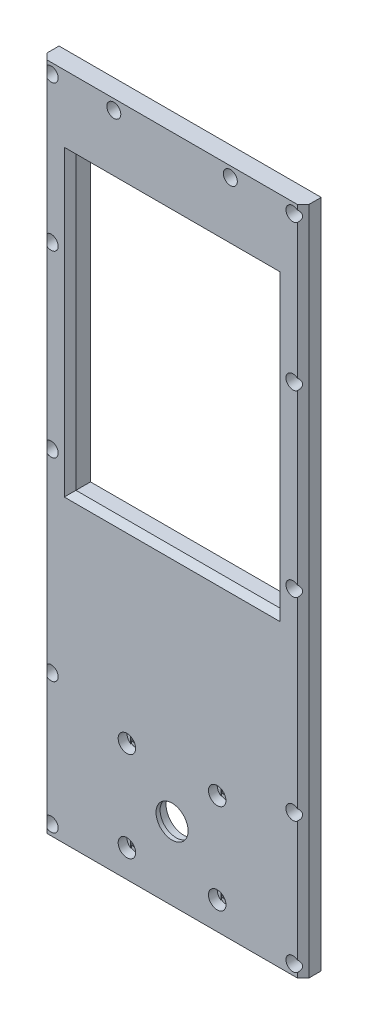
SolidWorks part; units mm, degrees
ref_plane "Front Plane" through (0, 0, 0) normal (0, 0, 1) x (1, 0, 0)
ref_plane "Top Plane" through (0, 0, 0) normal (0, 1, 0) x (1, 0, 0)
ref_plane "Right Plane" through (0, 0, 0) normal (1, 0, 0) x (0, 0, -1)
sketch "Sketch1" plane through (0, 0, 0) normal (0, 0, 1) x (1, 0, 0)
  line L1 (-45, -115) -> (45, -115)
  line L2 (-45, -115) -> (-45, 115)
  line L3 (-45, 115) -> (45, 115)
  line L4 (45, -115) -> (45, 115)
  line L5 (-45, -115) -> (45, 115) construction
  line L6 (-45, 115) -> (45, -115) construction
  line L7 (-38, -108) -> (38, -108)
  line L8 (-38, -108) -> (-38, 108)
  line L9 (-38, 108) -> (38, 108)
  line L10 (38, -108) -> (38, 108)
  line L11 (-38, -108) -> (38, 108) construction
  line L12 (-38, 108) -> (38, -108) construction
  point P0 (0, 0)
  point P6 (0, 0)
  dimension "D1" = 230
  dimension "D2" = 90
  dimension "D3" = 7
  dimension "D4" = 7
extrude "Boss-Extrude1" add sketch "Sketch1" along normal blind 7
sketch "Sketch2" plane through (0, 0, 7) normal (0, 0, 1) x (1, 0, 0)
  line L0 (38, -108) -> (38, 108) construction
  line L1 (-38, -108) -> (38, -108)
  line L2 (-38, -108) -> (-38, -58)
  line L3 (-38, -58) -> (38, -58)
  line L4 (38, -108) -> (38, -58)
  dimension "D1" = 50
extrude "Boss-Extrude2" add sketch "Sketch2" against normal up to surface (7 mm away) up to face at (0, 0, 0)
sketch "Sketch3" plane through (0, 0, 0) normal (0, 0, -1) x (-1, 0, 0)
  line L0 (0, -115) -> (0, -90) construction
  line L1 (45, -115) -> (-45, -115) construction
  circle A0 centre (0, -90) radius 5.5
  dimension "D1" = 11
  dimension "D2" = 25
extrude "Cut-Extrude1" cut sketch "Sketch3" against normal through all
sketch "Sketch4" plane through (0, 0, 0) normal (0, 0, -1) x (-1, 0, 0)
  circle A0 centre (0, -90) radius 6.05
  dimension "D1" = 12.1
extrude "Cut-Extrude2" cut sketch "Sketch4" against normal offset from surface (5.6 mm away) 1.4 up to face at (-5.5, -90, 7)
sketch "Sketch5" plane through (0, 0, 0) normal (0, 0, -1) x (-1, 0, 0)
  circle A0 centre (0, -90) radius 12
  dimension "D1" = 24
extrude "Cut-Extrude3" cut sketch "Sketch5" against normal offset from surface (3 mm away) 2.6 up to face at (-6.05, -90, 5.6)
sketch "Sketch6" plane through (0, 0, 0) normal (0, 0, -1) x (-1, 0, 0)
  line L1 (-15.5, -105.5) -> (15.5, -105.5) construction
  line L2 (-15.5, -105.5) -> (-15.5, -74.5) construction
  line L3 (-15.5, -74.5) -> (15.5, -74.5) construction
  line L4 (15.5, -105.5) -> (15.5, -74.5) construction
  line L5 (-15.5, -105.5) -> (15.5, -74.5) construction
  line L6 (-15.5, -74.5) -> (15.5, -105.5) construction
  circle A0 centre (-15.5, -74.5) radius 1.7
  circle A1 centre (15.5, -74.5) radius 1.7
  circle A2 centre (15.5, -105.5) radius 1.7
  circle A3 centre (-15.5, -105.5) radius 1.7
  point P0 (0, -90)
  dimension "D2" = 3.4
  dimension "D1" = 31
extrude "Cut-Extrude4" cut sketch "Sketch6" against normal through all
sketch "Sketch7" plane through (0, 0, 0) normal (0, 0, -1) x (-1, 0, 0)
  line L1 (-30, -112.5) -> (30, -112.5)
  line L2 (-30, -112.5) -> (-30, -67.5)
  line L3 (-30, -67.5) -> (30, -67.5)
  line L4 (30, -112.5) -> (30, -67.5)
  line L5 (-30, -112.5) -> (30, -67.5) construction
  line L6 (-30, -67.5) -> (30, -112.5) construction
  point P0 (0, -90)
  dimension "D1" = 60
  dimension "D2" = 45
extrude "Cut-Extrude5" cut sketch "Sketch7" against normal blind 1
sketch "Sketch8" plane through (0, 0, 7) normal (0, 0, 1) x (1, 0, 0)
  circle A0 centre (-15.5, -74.5) radius 3
  circle A1 centre (15.5, -74.5) radius 3
  circle A2 centre (15.5, -105.5) radius 3
  circle A3 centre (-15.5, -105.5) radius 3
  dimension "D1" = 6
extrude "Cut-Extrude6" cut sketch "Sketch8" against normal blind 3
sketch "Sketch9" plane through (0, 0, 7) normal (0, 0, 1) x (1, 0, 0)
  line L0 (-45, 115) -> (-45, -115) construction
  line L1 (-41.5, -111.5) -> (41.5, -111.5) construction
  line L2 (-41.5, -111.5) -> (-41.5, 111.5) construction
  line L3 (-41.5, 111.5) -> (41.5, 111.5) construction
  line L4 (41.5, -111.5) -> (41.5, 111.5) construction
  line L5 (-41.5, -111.5) -> (41.5, 111.5) construction
  line L6 (-41.5, 111.5) -> (41.5, -111.5) construction
  line L7 (45, 115) -> (-45, 115) construction
  circle A0 centre (-41.5, 111.5) radius 1.45
  circle A1 centre (41.5, 111.5) radius 1.45
  circle A4 centre (-41.5, -111.5) radius 1.45
  circle A5 centre (41.5, -111.5) radius 1.45
  circle A6 centre (-41.5, 61.5) radius 1.45
  circle A7 centre (41.5, 61.5) radius 1.45
  circle A8 centre (41.5, -66.5) radius 1.45
  circle A9 centre (-41.5, -66.5) radius 1.45
  circle A10 centre (-41.5, 0) radius 1.45
  circle A11 centre (41.5, 0) radius 1.45
  point P0 (0, 0)
  dimension "D3" = 2.9
  dimension "D1" = 3.5
  dimension "D2" = 3.5
  dimension "D4" = 45
  dimension "D5" = 50
extrude "Cut-Extrude7" cut sketch "Sketch9" against normal through all
sketch "Sketch10" plane through (0, 0, 7) normal (0, 0, 1) x (1, 0, 0)
  circle A0 centre (-41.5, 111.5) radius 2.4
  circle A1 centre (41.5, 61.5) radius 2.4
  circle A2 centre (-41.5, 61.5) radius 2.4
  circle A3 centre (41.5, 111.5) radius 2.4
  circle A4 centre (-41.5, -111.5) radius 2.4
  circle A5 centre (41.5, -111.5) radius 2.4
  circle A6 centre (-41.5, -66.5) radius 2.4
  circle A7 centre (41.5, -66.5) radius 2.4
  circle A8 centre (-41.5, 0) radius 2.4
  circle A9 centre (41.5, 0) radius 2.4
  dimension "D1" = 4.8
extrude "Cut-Extrude8" cut sketch "Sketch10" against normal blind 5
chamfer "Chamfer1" distance 2 angle 45 2 edges at (-45, 0, 7) (45, 0, 7)
sketch "Sketch11" plane through (0, 0, 7) normal (0, 0, 1) x (1, 0, 0)
  line L0 (38, -58) -> (38, 108) construction
  line L1 (-38, -58) -> (38, -58)
  line L2 (-38, -58) -> (-38, -36.4)
  line L3 (-38, -36.4) -> (38, -36.4)
  line L4 (38, -58) -> (38, -36.4)
  line L5 (-43, -115) -> (43, -115) construction
  dimension "D1" = 78.6
extrude "Boss-Extrude3" add sketch "Sketch11" against normal up to surface (7 mm away) up to face at (-40.05, 0, 0)
sketch "Sketch12" plane through (0, 0, 7) normal (0, 0, 1) x (1, 0, 0)
  line L0 (-41.5, 111.5) -> (41.5, 111.5) construction
  line L1 (-20, 111.5) -> (20, 111.5) construction
  circle A0 centre (-20, 111.5) radius 1.45
  circle A1 centre (20, 111.5) radius 1.45
  circle A2 centre (-41.5, 111.5) radius 1.45 construction
  point P7 (0, 111.5)
  dimension "D1" = 40
extrude "Cut-Extrude9" cut sketch "Sketch12" against normal through all
sketch "Sketch13" plane through (0, 0, 7) normal (0, 0, 1) x (1, 0, 0)
  circle A0 centre (-20, 111.5) radius 2.4
  circle A1 centre (20, 111.5) radius 2.4
  circle A2 centre (-41.5, 111.5) radius 2.4 construction
extrude "Cut-Extrude10" cut sketch "Sketch13" against normal up to surface (5 mm away) up to face at (-39.1, 111.5, 2)
chamfer "Chamfer2" distance 0.8 angle 45 12 edges at (0, -115, 0) (-45, 0, 0) (0, 115, 0) (45, 0, 0) (38, 35.8, 7) (0, 108, 7) (-38, 35.8, 7) (0, -36.4, 7) (-38, 35.8, 0) (0, 108, 0) (38, 35.8, 0) (0, -36.4, 0)
sketch "Sketch14" plane through (0, 0, 2) normal (0, 0, 1) x (1, 0, 0)
  line L2 (-42.95, -68.4125) -> (-42.95, -64.5875)
  line L4 (-40.05, -68.4125) -> (-40.05, -64.5875)
  line L5 (-42.95, -68.4125) -> (-40.05, -64.5875) construction
  line L6 (-42.95, -64.5875) -> (-40.05, -68.4125) construction
  line L14 (-42.95, -113.4125) -> (-42.95, -109.5875)
  line L16 (-40.05, -113.4125) -> (-40.05, -109.5875)
  line L17 (-42.95, -113.4125) -> (-40.05, -109.5875) construction
  line L18 (-42.95, -109.5875) -> (-40.05, -113.4125) construction
  line L26 (-42.95, 59.5875) -> (-42.95, 63.4125)
  line L28 (-40.05, 59.5875) -> (-40.05, 63.4125)
  line L29 (-42.95, 59.5875) -> (-40.05, 63.4125) construction
  line L30 (-42.95, 63.4125) -> (-40.05, 59.5875) construction
  line L32 (-21.45, 109.5875) -> (-21.45, 113.4125)
  line L34 (-18.55, 109.5875) -> (-18.55, 113.4125)
  line L35 (-21.45, 109.5875) -> (-18.55, 113.4125) construction
  line L36 (-21.45, 113.4125) -> (-18.55, 109.5875) construction
  line L38 (-42.95, 109.5875) -> (-42.95, 113.4125)
  line L40 (-40.05, 109.5875) -> (-40.05, 113.4125)
  line L41 (-42.95, 109.5875) -> (-40.05, 113.4125) construction
  line L42 (-42.95, 113.4125) -> (-40.05, 109.5875) construction
  arc A0 (-43, -68.3735) -> (-43, -64.6265) centre (-41.5, -66.5) ccw construction
  circle A2 centre (-41.5, -111.5) radius 2.4 construction
  circle A4 centre (-41.5, 61.5) radius 2.4 construction
  circle A5 centre (-20, 111.5) radius 2.4 construction
  circle A6 centre (-41.5, 111.5) radius 2.4 construction
  circle A7 centre (-41.5, 111.5) radius 1.45 construction
  circle A8 centre (-20, 111.5) radius 1.45 construction
  circle A9 centre (-41.5, 61.5) radius 1.45 construction
  circle A10 centre (-41.5, -66.5) radius 1.45 construction
  circle A12 centre (-41.5, -111.5) radius 1.45 construction
  arc A16 (-21.45, 109.5875) -> (-18.55, 109.5875) centre (-20, 111.5) ccw
  arc A17 (-40.05, 113.4125) -> (-42.95, 113.4125) centre (-41.5, 111.5) ccw
  arc A18 (-40.05, 63.4125) -> (-42.95, 63.4125) centre (-41.5, 61.5) ccw
  arc A20 (-42.95, -68.4125) -> (-40.05, -68.4125) centre (-41.5, -66.5) ccw
  arc A22 (-40.05, -109.5875) -> (-42.95, -109.5875) centre (-41.5, -111.5) ccw
  arc A23 (-42.95, 109.5875) -> (-40.05, 109.5875) centre (-41.5, 111.5) ccw
  arc A24 (-18.55, 113.4125) -> (-21.45, 113.4125) centre (-20, 111.5) ccw
  arc A25 (-42.95, 59.5875) -> (-40.05, 59.5875) centre (-41.5, 61.5) ccw
  arc A26 (-40.05, -64.5875) -> (-42.95, -64.5875) centre (-41.5, -66.5) ccw
  arc A29 (-42.95, -113.4125) -> (-40.05, -113.4125) centre (-41.5, -111.5) ccw
  point P0 (-41.5, -66.5)
  point P17 (-41.5, -111.5)
  point P33 (-41.5, 61.5)
  point P41 (-20, 111.5)
  point P49 (-41.5, 111.5)
extrude "Cut-Extrude11" cut sketch "Sketch14" against normal blind 0.2
sketch "Sketch15" plane through (0, 0, 1.8) normal (0, 0, 1) x (1, 0, 0)
  line L0 (-40.05, -111.5) -> (-40.05, -109.5875) construction
  line L1 (-42.95, -112.95) -> (-40.05, -112.95)
  line L2 (-42.95, -112.95) -> (-42.95, -110.05)
  line L3 (-42.95, -110.05) -> (-40.05, -110.05)
  line L4 (-40.05, -112.95) -> (-40.05, -110.05)
  line L5 (-42.95, -112.95) -> (-40.05, -110.05) construction
  line L6 (-42.95, -110.05) -> (-40.05, -112.95) construction
  line L7 (-40.05, 61.5) -> (-40.05, 63.4125) construction
  line L8 (-42.95, -67.95) -> (-40.05, -67.95)
  line L9 (-42.95, -67.95) -> (-42.95, -65.05)
  line L10 (-42.95, -65.05) -> (-40.05, -65.05)
  line L11 (-40.05, -67.95) -> (-40.05, -65.05)
  line L12 (-42.95, -67.95) -> (-40.05, -65.05) construction
  line L13 (-42.95, -65.05) -> (-40.05, -67.95) construction
  line L14 (-42.95, 60.05) -> (-40.05, 60.05)
  line L15 (-42.95, 60.05) -> (-42.95, 62.95)
  line L16 (-42.95, 62.95) -> (-40.05, 62.95)
  line L17 (-40.05, 60.05) -> (-40.05, 62.95)
  line L18 (-42.95, 60.05) -> (-40.05, 62.95) construction
  line L19 (-42.95, 62.95) -> (-40.05, 60.05) construction
  line L20 (-40.05, 109.5875) -> (-40.05, 113.4125) construction
  line L21 (-42.95, 110.05) -> (-40.05, 110.05)
  line L22 (-42.95, 110.05) -> (-42.95, 112.95)
  line L23 (-42.95, 112.95) -> (-40.05, 112.95)
  line L24 (-40.05, 110.05) -> (-40.05, 112.95)
  line L25 (-42.95, 110.05) -> (-40.05, 112.95) construction
  line L26 (-42.95, 112.95) -> (-40.05, 110.05) construction
  line L27 (-18.55, 109.5875) -> (-18.55, 113.4125) construction
  line L28 (-21.45, 110.05) -> (-18.55, 110.05)
  line L29 (-21.45, 110.05) -> (-21.45, 112.95)
  line L30 (-21.45, 112.95) -> (-18.55, 112.95)
  line L31 (-18.55, 110.05) -> (-18.55, 112.95)
  line L32 (-21.45, 110.05) -> (-18.55, 112.95) construction
  line L33 (-21.45, 112.95) -> (-18.55, 110.05) construction
  arc A0 (-40.05, -66.5) -> (-42.95, -66.5) centre (-41.5, -66.5) ccw construction
  arc A1 (-40.05, 61.5) -> (-42.95, 61.5) centre (-41.5, 61.5) ccw construction
  arc A2 (-18.55, 111.5) -> (-21.45, 111.5) centre (-20, 111.5) ccw construction
  arc A3 (-40.05, 111.5) -> (-42.95, 111.5) centre (-41.5, 111.5) ccw construction
  point P0 (-41.5, -111.5)
  point P8 (-41.5, -66.5)
  point P17 (-41.5, 61.5)
  point P28 (-41.5, 111.5)
  point P36 (-20, 111.5)
extrude "Cut-Extrude12" cut sketch "Sketch15" against normal blind 0.2
sketch "Sketch16" plane through (0, 0, 4) normal (0, 0, 1) x (1, 0, 0)
  line L2 (-17.2, -76.9718) -> (-17.2, -72.0282)
  line L4 (-13.8, -76.9718) -> (-13.8, -72.0282)
  line L5 (-17.2, -76.9718) -> (-13.8, -72.0282) construction
  line L6 (-17.2, -72.0282) -> (-13.8, -76.9718) construction
  line L8 (-17.2, -107.9718) -> (-17.2, -103.0282)
  line L10 (-13.8, -107.9718) -> (-13.8, -103.0282)
  line L11 (-17.2, -107.9718) -> (-13.8, -103.0282) construction
  line L12 (-17.2, -103.0282) -> (-13.8, -107.9718) construction
  circle A0 centre (-15.5, -74.5) radius 3 construction
  circle A1 centre (-15.5, -105.5) radius 3 construction
  circle A2 centre (-15.5, -105.5) radius 1.7 construction
  circle A3 centre (-15.5, -74.5) radius 1.7 construction
  circle A4 centre (-15.5, -105.5) radius 3 construction
  circle A5 centre (-15.5, -74.5) radius 3 construction
  arc A6 (-13.8, -103.0282) -> (-17.2, -103.0282) centre (-15.5, -105.5) ccw
  arc A7 (-17.2, -76.9718) -> (-13.8, -76.9718) centre (-15.5, -74.5) ccw
  arc A8 (-13.8, -72.0282) -> (-17.2, -72.0282) centre (-15.5, -74.5) ccw
  arc A9 (-17.2, -107.9718) -> (-13.8, -107.9718) centre (-15.5, -105.5) ccw
  point P0 (-15.5, -74.5)
  point P8 (-15.5, -105.5)
extrude "Cut-Extrude13" cut sketch "Sketch16" against normal blind 0.2
sketch "Sketch17" plane through (0, 0, 3.8) normal (0, 0, 1) x (1, 0, 0)
  line L0 (-13.8, -76.9718) -> (-13.8, -72.0282) construction
  line L1 (-17.2, -76.2) -> (-13.8, -76.2)
  line L2 (-17.2, -76.2) -> (-17.2, -72.8)
  line L3 (-17.2, -72.8) -> (-13.8, -72.8)
  line L4 (-13.8, -76.2) -> (-13.8, -72.8)
  line L5 (-17.2, -76.2) -> (-13.8, -72.8) construction
  line L6 (-17.2, -72.8) -> (-13.8, -76.2) construction
  line L7 (-13.8, -107.9718) -> (-13.8, -103.0282) construction
  line L8 (-17.2, -107.2) -> (-13.8, -107.2)
  line L9 (-17.2, -107.2) -> (-17.2, -103.8)
  line L10 (-17.2, -103.8) -> (-13.8, -103.8)
  line L11 (-13.8, -107.2) -> (-13.8, -103.8)
  line L12 (-17.2, -107.2) -> (-13.8, -103.8) construction
  line L13 (-17.2, -103.8) -> (-13.8, -107.2) construction
  arc A0 (-13.8, -105.5) -> (-17.2, -105.5) centre (-15.5, -105.5) ccw construction
  arc A1 (-13.8, -74.5) -> (-17.2, -74.5) centre (-15.5, -74.5) ccw construction
  point P0 (-15.5, -74.5)
  point P8 (-15.5, -105.5)
extrude "Cut-Extrude14" cut sketch "Sketch17" against normal blind 0.2
mirror "Mirror1" about plane through (0, 0, 0) normal (1, 0, 0) of "Cut-Extrude12", "Cut-Extrude13", "Cut-Extrude14", "Cut-Extrude11"
sketch "Sketch18" plane through (0, 0, 7) normal (0, 0, 1) x (1, 0, 0)
  line L0 (38.8, 108.8) -> (38.8, -37.2) construction
  line L1 (-38.8, 108.8) -> (38.8, 108.8)
  line L2 (-38.8, 108.8) -> (-38.8, 70.8)
  line L3 (-38.8, 70.8) -> (38.8, 70.8)
  line L4 (38.8, 108.8) -> (38.8, 70.8)
  dimension "D1" = 38
extrude "Boss-Extrude4" add sketch "Sketch18" against normal up to surface (7 mm away) up to face at (0, 35.8, 0)
chamfer "Chamfer3" distance 0.8 angle 45 1 edges at (0, 70.8, 7)
sketch "Sketch19" plane through (0, 0, 7) normal (0, 0, 1) x (1, 0, 0)
  line L1 (-38.8, 71.6) -> (38.8, 71.6)
  line L2 (-38.8, 71.6) -> (-38.8, -37.2)
  line L3 (-38.8, -37.2) -> (38.8, -37.2)
  line L4 (38.8, 71.6) -> (38.8, -37.2)
extrude "Boss-Extrude5" add sketch "Sketch19" against normal up to surface (7 mm away) up to face at (0, 16.8, 0)
sketch "Sketch20" plane through (0, 0, 2) normal (0, 0, 1) x (1, 0, 0)
  line L2 (-42.95, -1.9125) -> (-42.95, 1.9125)
  line L4 (-40.05, -1.9125) -> (-40.05, 1.9125)
  line L5 (-42.95, -1.9125) -> (-40.05, 1.9125) construction
  line L6 (-42.95, 1.9125) -> (-40.05, -1.9125) construction
  arc A0 (-43, -1.8735) -> (-43, 1.8735) centre (-41.5, 0) ccw construction
  circle A1 centre (-41.5, 0) radius 1.45 construction
  arc A2 (-42.95, -1.9125) -> (-40.05, -1.9125) centre (-41.5, 0) ccw
  arc A3 (-40.05, 1.9125) -> (-42.95, 1.9125) centre (-41.5, 0) ccw
  point P0 (-41.5, 0)
extrude "Cut-Extrude15" cut sketch "Sketch20" against normal blind 0.2
sketch "Sketch21" plane through (0, 0, 1.8) normal (0, 0, 1) x (1, 0, 0)
  line L0 (-40.05, -1.9125) -> (-40.05, 1.9125) construction
  line L1 (-42.95, -1.45) -> (-40.05, -1.45)
  line L2 (-42.95, -1.45) -> (-42.95, 1.45)
  line L3 (-42.95, 1.45) -> (-40.05, 1.45)
  line L4 (-40.05, -1.45) -> (-40.05, 1.45)
  line L5 (-42.95, -1.45) -> (-40.05, 1.45) construction
  line L6 (-42.95, 1.45) -> (-40.05, -1.45) construction
  arc A0 (-40.05, 0) -> (-42.95, 0) centre (-41.5, 0) ccw construction
  point P0 (-41.5, 0)
extrude "Cut-Extrude16" cut sketch "Sketch21" against normal blind 0.2
mirror "Mirror2" about plane through (0, 0, 0) normal (1, 0, 0) of "Cut-Extrude16", "Cut-Extrude15"
sketch "Sketch22" plane through (0, 0, 7) normal (0, 0, 1) x (1, 0, 0)
  line L0 (-43, -115) -> (43, -115) construction
  line L1 (-35, -10) -> (35, -10)
  line L2 (-35, -10) -> (-35, 90)
  line L3 (-35, 90) -> (35, 90)
  line L4 (35, -10) -> (35, 90)
  line L5 (-35, -10) -> (35, 90) construction
  line L6 (-35, 90) -> (35, -10) construction
  point P0 (0, 40)
  point P5 (0, 0)
  dimension "D1" = 70
  dimension "D2" = 100
  dimension "D3" = 155
extrude "Cut-Extrude17" cut sketch "Sketch22" against normal through all
chamfer "Chamfer4" distance 2 angle 45 4 edges at (-35, 40, 7) (0, -10, 7) (35, 40, 7) (0, 90, 7)
